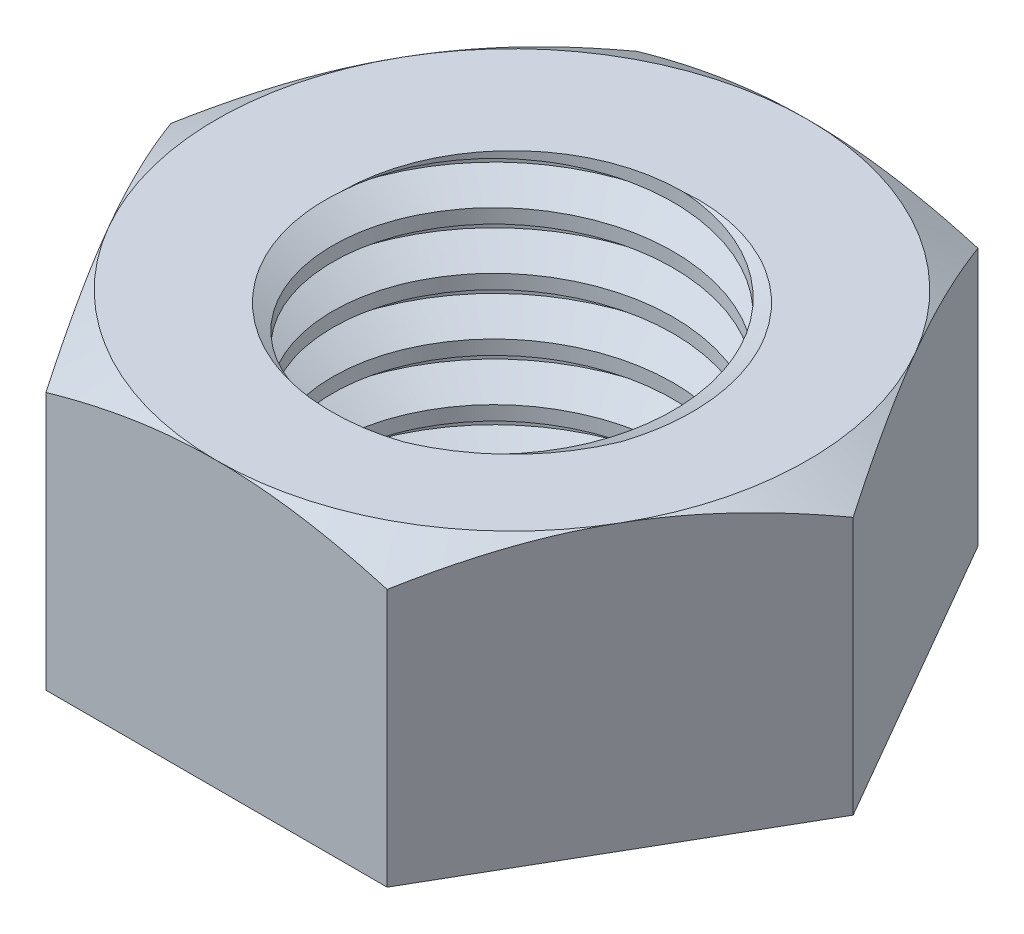
SolidWorks part; units mm, degrees
ref_plane "Front Plane" through (0, 0, 0) normal (0, 0, 1) x (1, 0, 0)
ref_plane "Top Plane" through (0, 0, 0) normal (0, 1, 0) x (1, 0, 0)
ref_plane "Right Plane" through (0, 0, 0) normal (1, 0, 0) x (0, 0, -1)
sketch "Sketch1" plane through (0, 0, 0) normal (0, 1, 0) x (1, 0, 0)
  line L1 (6, -10.3923) -> (12, 0)
  line L2 (12, 0) -> (6, 10.3923)
  line L3 (6, 10.3923) -> (-6, 10.3923)
  line L4 (-6, 10.3923) -> (-12, 0)
  line L5 (-12, 0) -> (-6, -10.3923)
  line L6 (-6, -10.3923) -> (6, -10.3923)
  circle A1 centre (0, 0) radius 10.3923 construction
  dimension "D1" = 24
extrude "Boss-Extrude1" add sketch "Sketch1" along normal blind 10
sketch "Sketch2" plane through (0, 0, 0) normal (1, 0, 0) x (0, 0, -1)
  line L0 (10.3923, 10) -> (13.8564, 10)
  line L1 (13.8564, 10) -> (13.8564, 8)
  line L2 (13.8564, 8) -> (10.3923, 10)
  line L3 (0, 0) -> (0, -50000) construction
  dimension "D1" = 30
  dimension "D2" = 2
revolve "Cut-Revolve1" cut sketch "Sketch2" angle 360 about L3
sketch "Sketch3" plane through (0, 10, 0) normal (0, 1, 0) x (1, 0, 0)
  circle A0 centre (0, 0) radius 6
  dimension "D1" = 12
extrude "Cut-Extrude1" cut sketch "Sketch3" against normal through all both and the other way through all
thread "Thread1" pitch 2 method cut profile "Thread Profile1" start angle 0, offset 4, length 0, pitch 2, diameter 12
ref_plane "Plane1" through (-6, 14, 0) normal (0, 0, 1) x (-1, 0, 0)
sketch "Thread Profile1" plane through (-6, 14, 0) normal (0, 0, 1) x (-1, 0, 0)
  line L0 (0, 0) -> (0, 2) construction
  line L1 (0, 0) -> (1.0825, 0.625)
  line L2 (1.0825, 0.625) -> (1.0825, 0.875)
  line L3 (1.0825, 0.875) -> (0, 1.5)
  line L4 (1.0825, 0.75) -> (0, 0.75) construction
  line L11 (0, 0) -> (0, 1.5)
  point P2 (0, 0)
  dimension "Pitch" = 2
  dimension "Profile_Angle" = 60
  dimension "Profile_Land" = 0.25
  dimension "Profile_Height" = 1.0825
